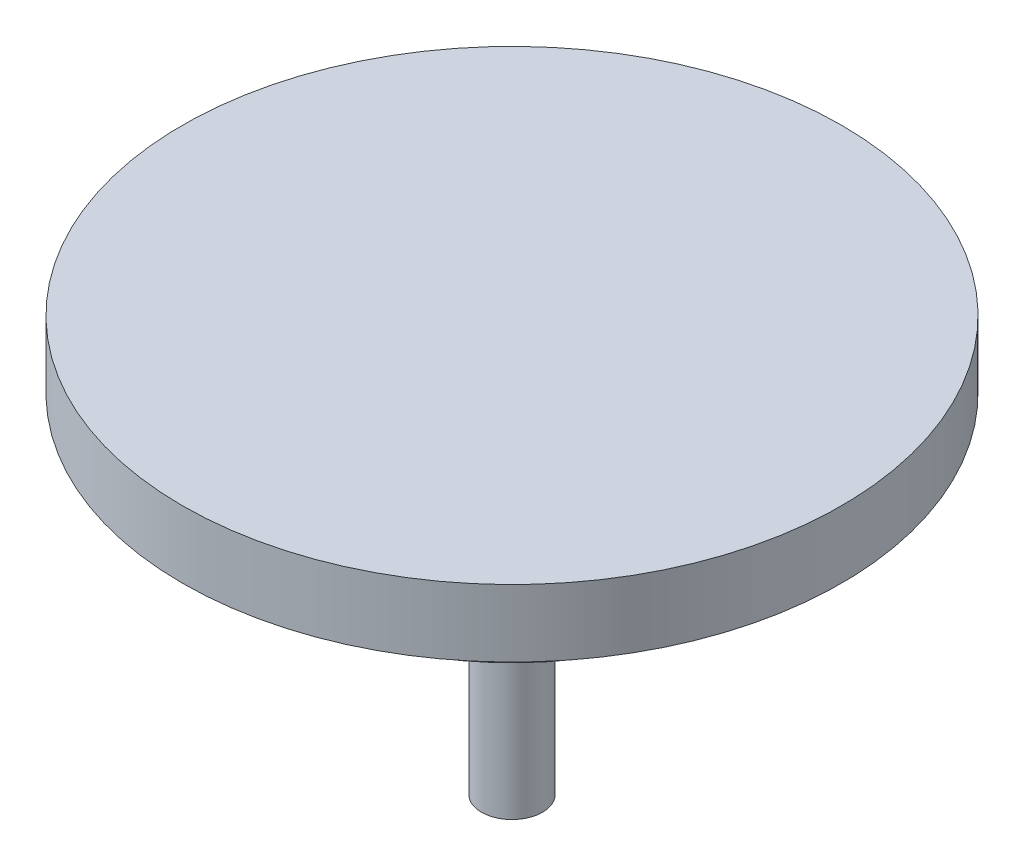
SolidWorks part; units mm, degrees
ref_plane "Front Plane" through (0, 0, 0) normal (0, 0, 1) x (1, 0, 0)
ref_plane "Top Plane" through (0, 0, 0) normal (0, 1, 0) x (1, 0, 0)
ref_plane "Right Plane" through (0, 0, 0) normal (1, 0, 0) x (0, 0, -1)
sketch "Sketch2" plane through (0, 0, 0) normal (0, 1, 0) x (1, 0, 0)
  circle A0 centre (0, 0) radius 54
  circle A1 centre (0, 0) radius 5
  dimension "D1" = 108
  dimension "D2" = 10
extrude "Boss-Extrude2" add sketch "Sketch2" against normal blind 57 contours A1 region at (0, 0, 0)
extrude "Boss-Extrude4" add sketch "Sketch2<5>" along normal blind 11 contours A0
sketch "Sketch2<5>" plane through (0, 0, 0) normal (0, 1, 0) x (1, 0, 0) same geometry as "Sketch2"
sketch "Sketch3" plane through (0, 0, 0) normal (0, -1, 0) x (1, 0, 0)
  line L0 (0, 0) -> (-64.4312, 0) construction
  line L1 (0, 55.8183) -> (0, 0) construction
  line L2 (0, 0) -> (0, -59.2532) construction
  circle A0 centre (-46, 19) radius 4
  arc A1 (-28.5657, -28) -> (0, 40) centre (0, 0) ccw
  spline S0 degree 2 poles (-28.5657, -28) (-4.3591, 1.6357) (0, 40) knots 0 0 0 1 1 1
  point P1 (0, 0)
  point P5 (0, 0)
  point P10 (0, 0)
  point P11 (0, 0)
  dimension "D1" = 11
  dimension "D3" = 8
  dimension "D4" = 80
  dimension "D5" = 28
  dimension "D2" = 46
  dimension "D7" = 19
extrude "Boss-Extrude6" add sketch "Sketch3" along normal blind 10
